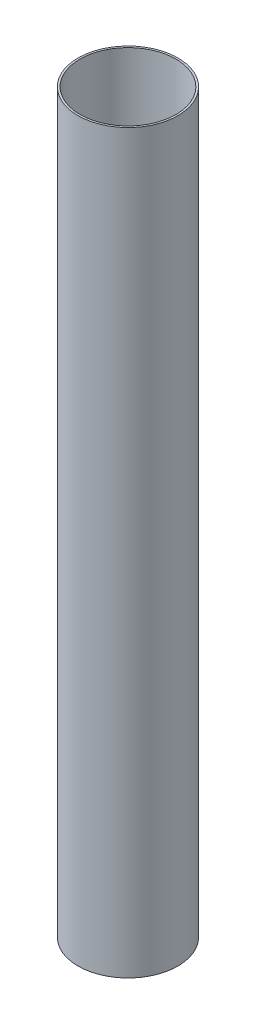
SolidWorks part; units mm, degrees
ref_plane "Front Plane" through (0, 0, 0) normal (0, 0, 1) x (1, 0, 0)
ref_plane "Top Plane" through (0, 0, 0) normal (0, 1, 0) x (1, 0, 0)
ref_plane "Right Plane" through (0, 0, 0) normal (1, 0, 0) x (0, 0, -1)
sketch "Sketch1" plane through (0, 0, 0) normal (0, 1, 0) x (1, 0, 0)
  circle A0 centre (0, 0) radius 39.624
  circle A1 centre (0, 0) radius 38.1
  dimension "D1" = 79.248
  dimension "D2" = 76.2
extrude "Boss-Extrude1" add sketch "Sketch1" along normal blind 584.2
